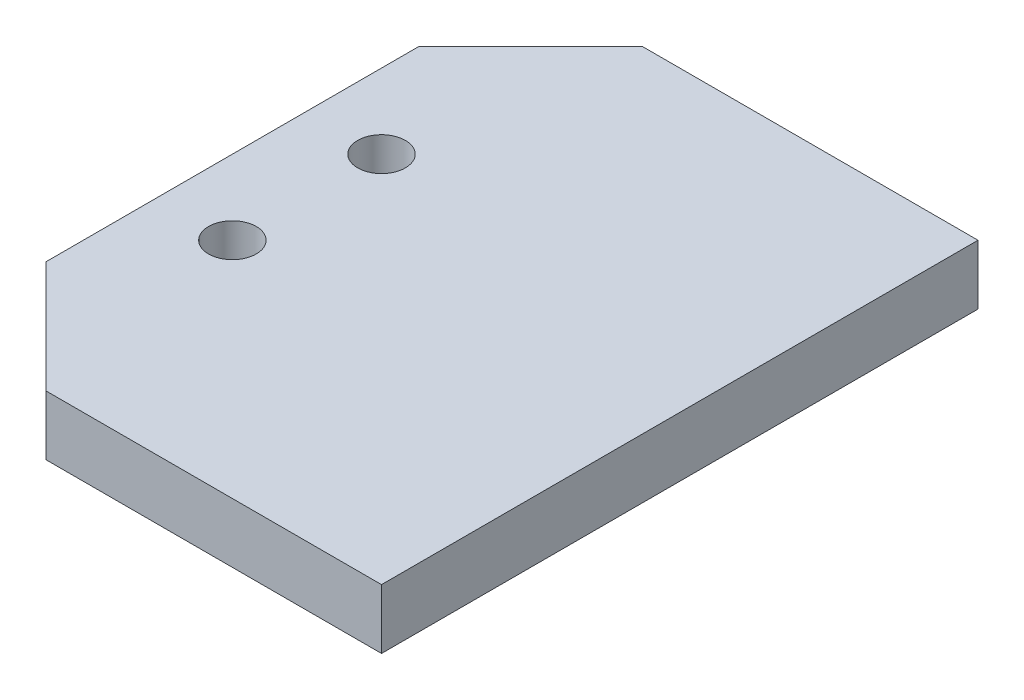
SolidWorks part; units mm, degrees
ref_plane "Front Plane" through (0, 0, 0) normal (0, 0, 1) x (1, 0, 0)
ref_plane "Top Plane" through (0, 0, 0) normal (0, 1, 0) x (1, 0, 0)
ref_plane "Right Plane" through (0, 0, 0) normal (1, 0, 0) x (0, 0, -1)
sketch "Sketch1" plane through (0, 0, 0) normal (0, 1, 0) x (1, 0, 0)
  line L0 (5, 25) -> (5, 15) construction
  line L1 (0, 0) -> (30, 0)
  line L2 (0, 0) -> (0, 40)
  line L3 (0, 40) -> (30, 40)
  line L4 (30, 0) -> (30, 40)
  line L5 (0, 30.2) -> (10, 30.2) construction
  line L6 (0, 30.2) -> (0, 9.8) construction
  line L7 (0, 9.8) -> (10, 9.8) construction
  line L8 (10, 30.2) -> (10, 9.8) construction
  line L9 (0, 30.2) -> (10, 9.8) construction
  line L10 (0, 9.8) -> (10, 30.2) construction
  circle A0 centre (5, 25) radius 1.6
  circle A1 centre (5, 15) radius 1.6
  point P9 (5, 20)
  point P10 (0, 20)
  point P11 (0, 20)
  dimension "D5" = 3.2
  dimension "D8" = 5
  dimension "D1" = 40
  dimension "D2" = 30
  dimension "D3" = 20.4
  dimension "D4" = 10
  dimension "D6" = 5.2
  dimension "D7" = 5.2
extrude "Boss-Extrude1" add sketch "Sketch1" along normal blind 4
chamfer "Chamfer1" distance 7.5 angle 45 2 edges at (0, 2, -40) (0, 2, 0)
